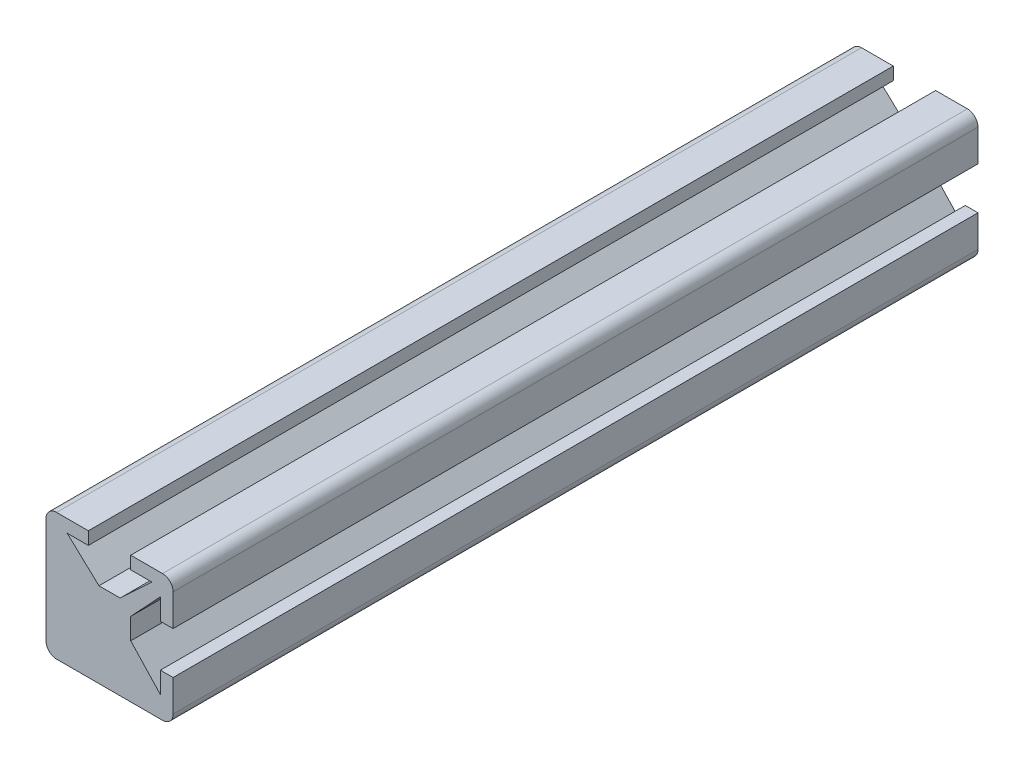
SolidWorks part; units mm, degrees
ref_plane "Plan de face" through (0, 0, 0) normal (0, 0, 1) x (1, 0, 0)
ref_plane "Plan de dessus" through (0, 0, 0) normal (0, 1, 0) x (1, 0, 0)
ref_plane "Plan de droite" through (0, 0, 0) normal (1, 0, 0) x (0, 0, -1)
sketch "Esquisse1" plane through (0, 0, 0) normal (0, 0, 1) x (1, 0, 0)
  line L0 (-6, 5) -> (-6, -5)
  line L1 (-5, 6) -> (5, 6)
  line L2 (-5, -6) -> (5, -6)
  line L3 (6, 5) -> (6, -5)
  line L4 (-5, 5) -> (5, -5) construction
  line L5 (5, 5) -> (-5, -5) construction
  arc A0 (-5, 6) -> (-6, 5) centre (-5, 5) ccw
  arc A1 (5, 6) -> (6, 5) centre (5, 5) cw
  arc A2 (6, -5) -> (5, -6) centre (5, -5) cw
  arc A3 (-5, -6) -> (-6, -5) centre (-5, -5) cw
  point P12 (0, 0)
  dimension "D1" = 1
  dimension "D2" = 1
  dimension "D4" = 1
  dimension "D3" = 12
extrude "Extrusion1" add sketch "Esquisse1" along normal mid plane 76
sketch "Esquisse3" plane through (0, 0, 38) normal (0, 0, 1) x (1, 0, 0)
  line L0 (6, 2) -> (4.8, 2)
  line L2 (4.8, 2) -> (4.8, 4)
  line L3 (2, 1) -> (2, -1)
  line L4 (4.8, -4) -> (4.8, -2)
  line L5 (4.8, -2) -> (6, -2)
  line L6 (6, -5) -> (6, 5) construction
  line L7 (4.8, 4) -> (2, 1)
  line L8 (6, 2) -> (6, -2)
  line L9 (4.8, -4) -> (2, -1)
  point P4 (6, 0)
  point P10 (6, 0)
  dimension "D1" = 4
  dimension "D2" = 1.2
  dimension "D3" = 4
  dimension "D4" = 2
  dimension "D5" = 2
extrude "Enlèv. mat.-Extru.1" cut sketch "Esquisse3" against normal through all
ref_axis "Axe1" through (0, 0, -1) along (0, 0, 1)
pattern_circular "Répétition circulaire1" count 2 every 90 about axis through (0, 0, -1) along (0, 0, 1) of "Enlèv. mat.-Extru.1"
